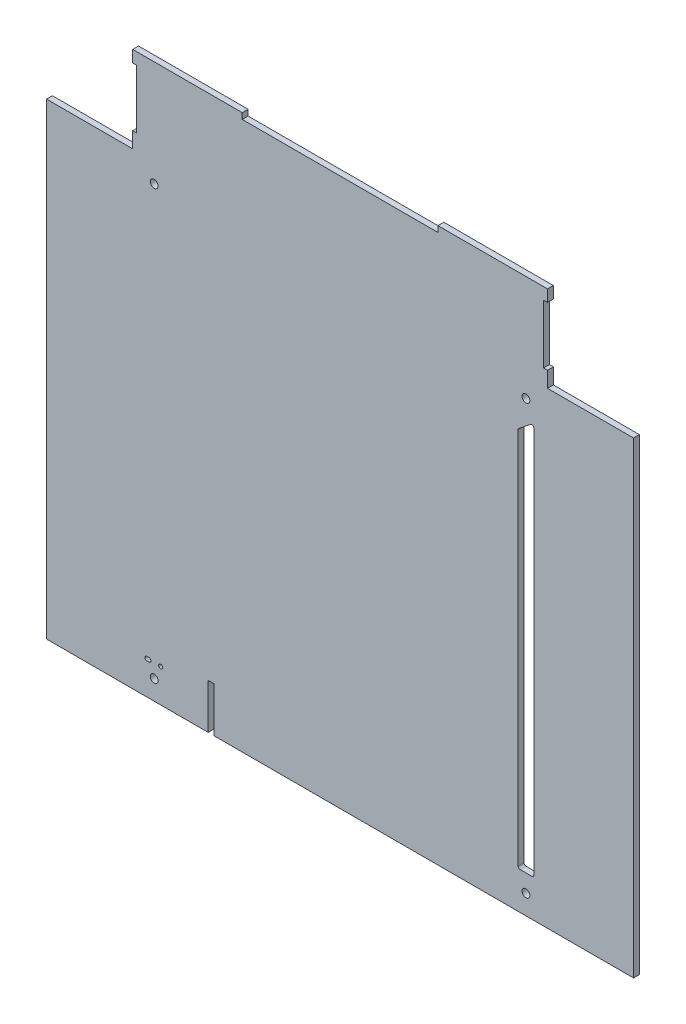
SolidWorks part; units mm, degrees
ref_plane "Front Plane" through (0, 0, 0) normal (0, 0, 1) x (1, 0, 0)
ref_plane "Top Plane" through (0, 0, 0) normal (0, 1, 0) x (1, 0, 0)
ref_plane "Right Plane" through (0, 0, 0) normal (1, 0, 0) x (0, 0, -1)
sketch "Sketch1" plane through (0, 0, 0) normal (0, 0, 1) x (1, 0, 0)
  line L0 (0, 0) -> (-206.9982, 0) construction
  line L1 (150, -119.5) -> (-150, -119.5)
  line L2 (150, -119.5) -> (150, 119.5)
  line L3 (150, 119.5) -> (-150, 119.5)
  line L4 (-150, -119.5) -> (-150, 119.5)
  line L5 (150, -119.5) -> (-150, 119.5) construction
  line L6 (150, 119.5) -> (-150, -119.5) construction
  line L7 (137.4477, -109.5) -> (-137.4477, -109.5) construction
  line L8 (137.4477, -109.5) -> (137.4477, 109.5) construction
  line L9 (137.4477, 109.5) -> (-137.4477, 109.5) construction
  line L10 (-137.4477, -109.5) -> (-137.4477, 109.5) construction
  line L11 (137.4477, -109.5) -> (-137.4477, 109.5) construction
  line L12 (137.4477, 109.5) -> (-137.4477, -109.5) construction
  line L13 (99, 100.5) -> (99, -100.5)
  line L14 (91, 94.1267) -> (91, -94.1267)
  line L15 (99, 100.5) -> (91, 94.1267)
  line L16 (99, -100.5) -> (91, -94.1267)
  line L17 (82, 112) -> (-82, 112)
  line L18 (95, 94.1267) -> (95, -94.1267) construction
  line L19 (-82, 112) -> (-75.7238, 107)
  line L20 (82, 112) -> (75.7238, 107)
  line L21 (137.4477, 112) -> (-137.4477, 112) construction
  line L22 (75.7238, 107) -> (-75.7238, 107)
  line L23 (99, -100.5) -> (91, -100.5)
  line L24 (91, -100.5) -> (91, -94.1267)
  line L25 (-64.4111, -119.5) -> (-67.4111, -119.5)
  line L26 (106, 119.5) -> (-106, 119.5)
  line L27 (106, 119.5) -> (106, 163.5)
  line L28 (106, 163.5) -> (-106, 163.5)
  line L29 (-106, 119.5) -> (-106, 163.5)
  line L30 (-67.4111, -119.5) -> (-67.4111, -96.5)
  line L31 (-67.4111, -96.5) -> (-64.4111, -96.5)
  line L32 (-64.4111, -96.5) -> (-64.4111, -119.5)
  circle A0 centre (-95, 109.5) radius 2
  circle A1 centre (95, 109.5) radius 2
  circle A2 centre (95, -109.5) radius 2
  circle A3 centre (-95, -109.5) radius 2
  point P0 (0, 0)
  point P5 (0, 0)
  point P40 (0, 0)
  dimension "D4" = 4
  dimension "D5" = 4
  dimension "D1" = 300
  dimension "D2" = 239
  dimension "D3" = 10
  dimension "D6" = 55
  dimension "D7" = 55
  dimension "D8" = 9
  dimension "D9" = 8
  dimension "D10" = 55
  dimension "D11" = 9
  dimension "D14" = 13
  dimension "D15" = 13
  dimension "D13" = 2.5
  dimension "D17" = 44
  dimension "D18" = 44
  dimension "D19" = 44
  dimension "D20" = 23
  dimension "D21" = 3
  dimension "D12" = 2.5
  dimension "D16" = 4
extrude "Boss-Extrude1" add sketch "Sketch1" along normal blind 3 contours L22 L20 L17 L19 | L4 L1 L2 L3 A2 A1 A0 L13 L16 L14 L15 L20 L22 L19 L17 A3 | L29 L3 L27 L28 region at (-2.107, -1.1042, 0) region at (0, 141.5, 0) region at (0, 109.5332, 0)
sketch "Schizzo1" plane through (0, 0, 0) normal (0, 0, -1) x (-1, 0, 0)
  line L0 (-106, 119.5) -> (-106, 163.5) construction
  line L1 (-106, 157.5) -> (-104, 157.5)
  line L2 (-106, 157.5) -> (-106, 127.5)
  line L3 (-106, 127.5) -> (-104, 127.5)
  line L4 (-104, 157.5) -> (-104, 127.5)
  line L5 (-105, 127.5) -> (-105, 157.5) construction
  line L6 (-106, 142.5) -> (-104, 142.5) construction
  line L7 (-106, 163.5) -> (106, 163.5) construction
  line L8 (0, 0) -> (0, 211.7309) construction
  line L9 (50, 160.5) -> (-50, 160.5)
  line L10 (50, 160.5) -> (50, 163.5)
  line L11 (50, 163.5) -> (-50, 163.5)
  line L12 (-50, 160.5) -> (-50, 163.5)
  line L13 (50, 160.5) -> (-50, 163.5) construction
  line L14 (50, 163.5) -> (-50, 160.5) construction
  line L15 (106, 142.5) -> (104, 142.5) construction
  line L16 (105, 127.5) -> (105, 157.5) construction
  line L17 (104, 157.5) -> (104, 127.5)
  line L18 (106, 127.5) -> (104, 127.5)
  line L19 (106, 157.5) -> (106, 127.5)
  line L20 (106, 157.5) -> (104, 157.5)
  point P8 (0, 162)
  point P23 (105, 142.5)
  point P516 (-105, 142.5)
  dimension "D1" = 6
  dimension "D2" = 30
  dimension "D3" = 2
  dimension "D4" = 100
  dimension "D5" = 3
extrude "Taglio-Estrusione1" cut sketch "Schizzo1" against normal blind 10
fillet "Raccordo1" radius 1 4 edges at (91, -100.5, 1.5) (99, -100.5, 1.5) (91, 94.1267, 1.5) (99, 100.5, 1.5)
sketch "Schizzo2" plane through (0, 0, 3) normal (0, 0, 1) x (1, 0, 0)
  line L0 (-67.4111, -96.5) -> (-64.4111, -96.5) construction
  line L1 (-98.6779, -102.5) -> (-91.6779, -102.5) construction
  line L2 (-98.6779, -102.5) -> (-98.6779, -96.5) construction
  line L3 (-98.6779, -96.5) -> (-91.6779, -96.5) construction
  line L4 (-91.6779, -102.5) -> (-91.6779, -96.5) construction
  line L5 (-95.1779, -96.5) -> (-95.1779, -102.5) construction
  line L6 (-98.6779, -99.5) -> (-91.6779, -99.5) construction
  line L7 (-98.6779, -102.5) -> (-97.6779, -102.5) construction
  line L8 (-98.6779, -101.4766) -> (-97.6779, -101.4766)
  line L9 (-98.6779, -103.5234) -> (-97.6779, -103.5234)
  circle A1 centre (-91.6779, -102.5) radius 1
  arc A2 (-98.6779, -101.4766) -> (-98.6779, -103.5234) centre (-98.6779, -102.5) ccw
  arc A3 (-97.6779, -103.5234) -> (-97.6779, -101.4766) centre (-97.6779, -102.5) ccw
  point P8 (-98.1779, -102.5)
  point P208 (-95.1779, -99.5)
  dimension "D2" = 2
  dimension "D3" = 7
  dimension "D4" = 6
extrude "Taglio-Estrusione2" cut sketch "Schizzo2" against normal blind 10 contours L9 A3 L8 A2 | A1 region at (-98.1779, -102.5, 3)
